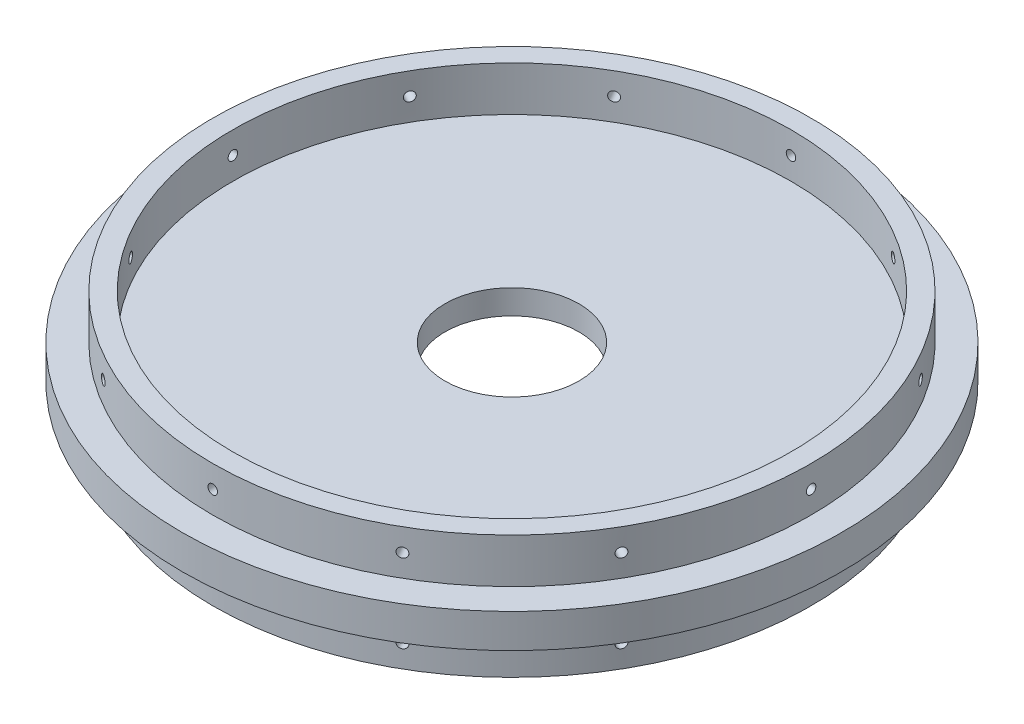
SolidWorks part; units mm, degrees
material "6061-T6 (SS)"
ref_plane "Front Plane" through (0, 0, 0) normal (0, 0, 1) x (1, 0, 0)
ref_plane "Top Plane" through (0, 0, 0) normal (0, 1, 0) x (1, 0, 0)
ref_plane "Right Plane" through (0, 0, 0) normal (1, 0, 0) x (0, 0, -1)
sketch "Sketch1" plane through (0, 0, 0) normal (0, 1, 0) x (1, 0, 0)
  circle A0 centre (0, 0) radius 93.726
  dimension "D1" = 187.452
extrude "Boss-Extrude1" add sketch "Sketch1" along normal mid plane 9.652
sketch "Sketch2" plane through (0, 0, 0) normal (0, 0, 1) x (1, 0, 0)
  line L0 (0, -18.3275) -> (0, 20.8308) construction
  line L1 (0, -4.826) -> (-25.4, -4.826)
  line L2 (-93.726, -4.826) -> (93.726, -4.826) construction
  line L3 (0, -4.826) -> (0, 1.27)
  spline S0 degree 3 poles (0, 1.27) (-5.1197, 1.5129) (-13.6852, -0.4966) (-22.1585, -2.9398) (-25.4, -4.826) knots 0 0 0 0 0.575799 1 1 1 1
  dimension "D1" = 25.4
  dimension "D2" = 6.096
revolve "Cut-Revolve1" cut sketch "Sketch2" angle 360 about L0
sketch "Sketch4" plane through (0, 4.826, 0) normal (0, 1, 0) x (1, 0, 0)
  circle A0 centre (0, 0) radius 85.09
  circle A1 centre (0, 0) radius 79.375
  dimension "D1" = 170.18
  dimension "D2" = 158.75
extrude "Boss-Extrude2" add sketch "Sketch4" along normal blind 12.7
ref_plane "Plane1" through (0, 0, -85.09) normal (0, 0, -1) x (-1, 0, 0)
sketch "Sketch5" plane through (0, 0, -85.09) normal (0, 0, -1) x (-1, 0, 0)
  line L0 (0, 19.2786) -> (0, -19.2786) construction
  line L1 (79.375, 17.526) -> (-79.375, 17.526) construction
  circle A0 centre (0, 11.176) radius 1.3525
  dimension "D1" = 2.7051
  dimension "D2" = 6.35
extrude "Cut-Extrude2" cut sketch "Sketch5" against normal blind 12.7
pattern_circular "CirPattern1" count 12 over 360 about axis through (0, 17.526, 0) along (0, -1, 0) of "Cut-Extrude2" reverse direction yes
mirror "Mirror2" about plane through (0, 0, 0) normal (0, 1, 0) of "CirPattern1", "Cut-Extrude2", "Boss-Extrude2"
sketch "Sketch6" plane through (0, 4.826, 0) normal (0, 1, 0) x (1, 0, 0)
  line L0 (-63.5, 0) -> (-69.85, 0)
  line L1 (0, -69.85) -> (0, -63.5)
  line L2 (0, -19.2786) -> (0, 19.2786) construction
  arc A0 (-69.85, 0) -> (0, -69.85) centre (0, 0) ccw
  arc A1 (-63.5, 0) -> (0, -63.5) centre (0, 0) ccw
  dimension "D1" = 69.85
  dimension "D2" = 63.5
  dimension "D3" = 90
extrude "Cut-Extrude3" [suppressed] cut sketch "Sketch6" against normal up to surface (9.652 mm away) up to face at (0, -4.826, -25.4)
sketch "Sketch7" plane through (0, -4.826, 0) normal (0, -1, 0) x (1, 0, 0)
  circle A0 centre (0, 0) radius 19.05
  dimension "D1" = 38.1
extrude "Cut-Extrude4" cut sketch "Sketch7" against normal through all
